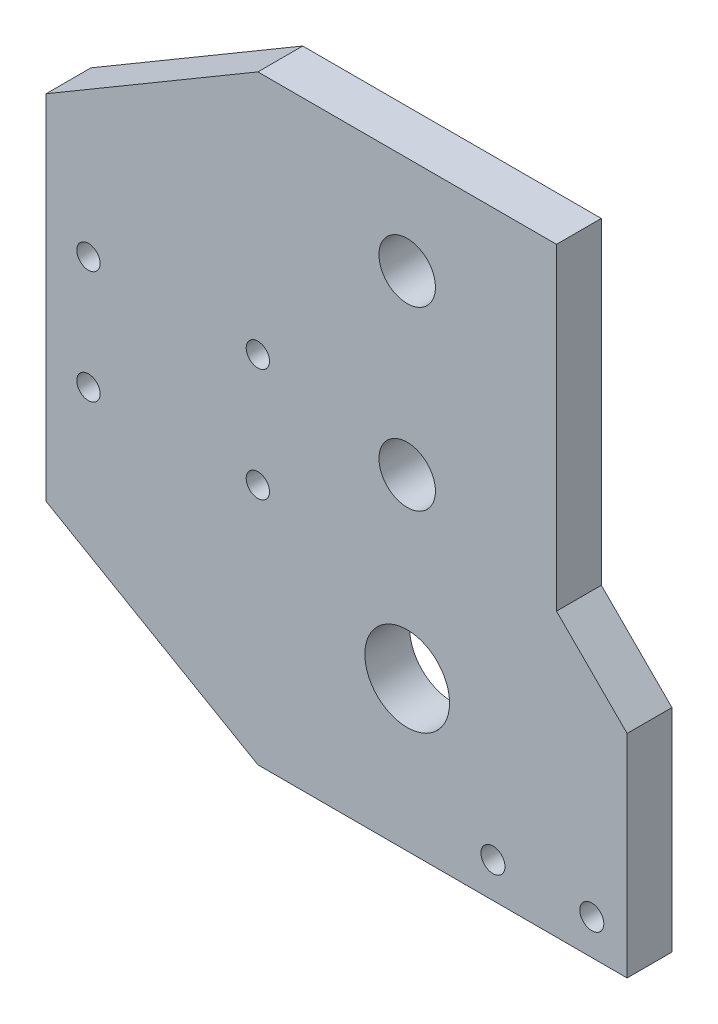
SolidWorks part; units mm, degrees
material "6061 Alloy"
ref_plane "Front Plane" through (0, 0, 0) normal (0, 0, 1) x (1, 0, 0)
ref_plane "Top Plane" through (0, 0, 0) normal (0, 1, 0) x (1, 0, 0)
ref_plane "Right Plane" through (0, 0, 0) normal (1, 0, 0) x (0, 0, -1)
sketch "Sketch2" plane through (0, 0, 0) normal (0, 0, 1) x (1, 0, 0)
  line L0 (0, 0) -> (0, -21.15) construction
  line L1 (-21.15, -21.15) -> (21.15, -21.15)
  line L2 (-21.15, -21.15) -> (-21.15, 63.85)
  line L3 (-21.15, 63.85) -> (21.15, 63.85)
  line L4 (21.15, -21.15) -> (21.15, 63.85)
  circle A0 centre (0, 0) radius 6
  circle A1 centre (0, 25) radius 4
  circle A2 centre (0, 50) radius 4
  dimension "D1" = 12
  dimension "D5" = 25
  dimension "D7" = 8
  dimension "D2" = 21.15
  dimension "D3" = 42.3
  dimension "D4" = 85
  dimension "D6" = 25
extrude "Boss-Extrude1" add sketch "Sketch2" along normal blind 6.35
sketch "Sketch8" plane through (0, 0, 6.35) normal (0, 0, 1) x (1, 0, 0)
  line L0 (-21.15, -21.15) -> (-51.15, -3.8295)
  line L1 (-51.15, -3.8295) -> (-51.15, 46.1705)
  line L2 (-51.15, 46.1705) -> (-21.15, 63.85)
  line L3 (-21.15, 63.85) -> (-21.15, -21.15) construction
  line L4 (-21.15, 63.85) -> (-21.15, -21.15)
  dimension "D2" = 60
  dimension "D3" = 30
  dimension "D4" = 50
extrude "Boss-Extrude2" add sketch "Sketch8" against normal up to surface (6.35 mm away) up to face at (4, 25, 0)
sketch "Sketch9" plane through (0, 0, 6.35) normal (0, 0, 1) x (1, 0, 0)
  line L0 (-51.15, 21.1705) -> (-33.15, 21.1705) construction
  line L1 (-51.15, 46.1705) -> (-51.15, -3.8295) construction
  line L3 (-45.15, 13.1705) -> (-21.15, 13.1705) construction
  line L4 (-45.15, 13.1705) -> (-45.15, 29.1705) construction
  line L5 (-45.15, 29.1705) -> (-21.15, 29.1705) construction
  line L6 (-21.15, 13.1705) -> (-21.15, 29.1705) construction
  line L7 (-45.15, 13.1705) -> (-21.15, 29.1705) construction
  line L8 (-45.15, 29.1705) -> (-21.15, 13.1705) construction
  point P4 (-21.15, 29.1705)
  point P5 (-45.15, 13.1705)
  point P6 (-45.15, 29.1705)
  point P7 (-21.15, 13.1705)
  dimension "D1" = 18
  dimension "D2" = 16
  dimension "D3" = 24
hole_wizard "Tap Drill for M4x0.7 Tap1" positions "Sketch9" profile "Sketch10" hole size "M4x0.7" standard "ANSI Metric" end condition through all
sketch "Sketch10" plane through (-21.15, 13.1705, 6.35) normal (1, 0, 0) x (0, -1, 0)
  line L0 (0, 0) -> (0, 6.35)
  line L1 (0, 6.35) -> (1.65, 6.35)
  line L2 (1.65, 6.35) -> (1.65, 0)
  line L5 (1.65, 0) -> (0, 0)
  line L11 (0, -6.35) -> (0, 107.95) construction
  dimension "Thru Hole Dia." = 3.3
  dimension "Thru Hole Depth" = 6.35
sketch "Sketch11" plane through (0, 0, 6.35) normal (0, 0, 1) x (1, 0, 0)
  line L0 (21.15, -21.15) -> (31.15, -21.15)
  line L1 (31.15, -21.15) -> (31.15, 8.85)
  line L2 (31.15, 8.85) -> (21.15, 18.85)
  line L3 (21.15, -21.15) -> (21.15, 63.85) construction
  line L4 (21.15, 18.85) -> (21.15, -21.15)
  point P4 (21.15, 19.7554)
  dimension "D1" = 10
  dimension "D2" = 30
  dimension "D3" = 45
extrude "Boss-Extrude3" add sketch "Sketch11" against normal up to surface (6.35 mm away) up to face at (-19.5, 29.1705, 0)
sketch "Sketch14" plane through (0, 0, 6.35) normal (0, 0, 1) x (1, 0, 0)
  line L0 (12.15, -16.15) -> (26.15, -16.15) construction
  line L1 (31.15, -21.15) -> (31.15, 8.85) construction
  line L2 (-21.15, -21.15) -> (31.15, -21.15) construction
  point P0 (12.15, -16.15)
  point P1 (26.15, -16.15)
  dimension "D1" = 14
  dimension "D2" = 5
  dimension "D3" = 5
hole_wizard "M3 Clearance Hole2" positions "Sketch14" profile "Sketch15" hole size "M3" standard "ANSI Metric" end condition through all
sketch "Sketch15" plane through (12.15, -16.15, 6.35) normal (1, 0, 0) x (0, -1, 0)
  line L0 (0, 0) -> (0, 6.35)
  line L1 (0, 6.35) -> (1.7, 6.35)
  line L2 (1.7, 6.35) -> (1.7, 0)
  line L5 (1.7, 0) -> (0, 0)
  line L11 (0, -6.35) -> (0, 107.95) construction
  dimension "Thru Hole Dia." = 3.4
  dimension "Thru Hole Depth" = 6.35
sketch "Sketch3" plane through (31.15, 0, 0) normal (-1, 0, 0) x (0, 0, 1)
  line L0 (6.35, -6) -> (6.35, 6) construction
  line L1 (6.35, 21) -> (6.35, 29) construction
  line L2 (6.35, 46) -> (6.35, 54) construction
  line L3 (6.35, -6) -> (6.35, 6) construction
  line L4 (6.35, 21) -> (6.35, 29) construction
  line L5 (6.35, 46) -> (6.35, 54) construction
  line L6 (3.175, 63.85) -> (3.175, -21.15) construction
  line L9 (6.35, 0) -> (3.175, 0) construction
  line L10 (6.35, 25) -> (3.175, 25) construction
  line L11 (6.35, 50) -> (3.175, 50) construction
  line L12 (6.35, -21.15) -> (0, -21.15) construction
  line L13 (6.35, 63.85) -> (0, 63.85) construction
  point P13 (3.175, 0)
  point P16 (3.175, 25)
  point P18 (3.175, 50)
  point P19 (0, 0)
  point P22 (0, 0)
  point P25 (0, 0)
  point P26 (3.175, 63.85)
